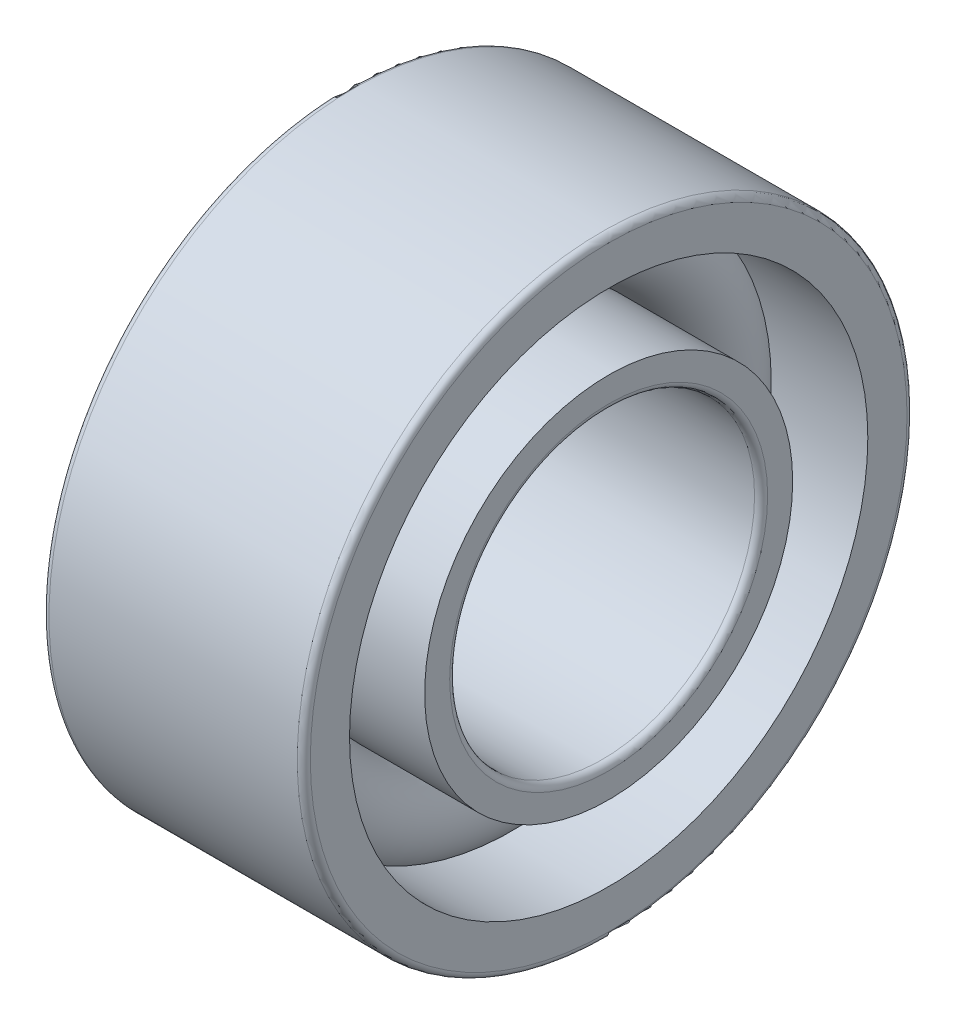
SolidWorks part; units mm, degrees
ref_plane "Plane1" through (0, 0, 0) normal (0, 0, 1) x (1, 0, 0)
ref_plane "Plane2" through (0, 0, 0) normal (0, 1, 0) x (1, 0, 0)
ref_plane "Plane3" through (0, 0, 0) normal (1, 0, 0) x (0, 0, -1)
other "Configuration Table"
sketch "Clipboard" plane through (0, 0, 0) normal (0, 0, 1) x (1, 0, 0)
  line L0 (-10, 0) -> (10, 0) construction
  line L1 (0, 0) -> (22.3471, -0.7804)
  line L2 (0, 0) -> (5.2468, 0.1832)
  line L3 (0, 0) -> (22.3471, -0.7804)
  line L4 (0, 0) -> (-22.3573, -0.3902)
sketch "CagSpiSke" plane through (0, 0, 0) normal (0, 0, 1) x (1, 0, 0)
  line L0 (0.2625, 5.075) -> (0.2625, 5.425)
  line L1 (0.2625, 5.425) -> (-0.2625, 5.425)
  line L2 (-0.2625, 5.425) -> (-0.2625, 5.075)
  line L3 (-0.2625, 5.075) -> (0.2625, 5.075)
  line L4 (-20.6375, 0) -> (20.6375, 0) construction
  line L5 (0, 0) -> (0, 23.7692) construction
revolve "CageSpine" add sketch "CagSpiSke" angle 0.001 about L4
ref_axis "Axis1" through (-50, 0, 0) along (1, 0, 0)
sketch "CagBalSke" plane through (0, 0, 0) normal (0, 0, 1) x (1, 0, 0)
  line L0 (-1.155, 5.25) -> (1.155, 5.25)
  line L1 (-1.905, 5.25) -> (1.905, 5.25) construction
  line L2 (-10, 0) -> (10, 0) construction
  line L3 (0, 0) -> (0, 24) construction
  arc A0 (1.155, 5.25) -> (-1.155, 5.25) centre (0, 5.25) cw
revolve "CageBall" [suppressed] add sketch "CagBalSke" angle 360 about L1 reverse direction yes
pattern_circular "CageBalls" [suppressed] count 2 every 180 about axis through (-50, 0, 0) along (1, 0, 0)
sketch "CagTrmODSke" plane through (0, 0, 0) normal (0, 0, 1) x (1, 0, 0)
  line L0 (1.156, 5.425) -> (1.156, 6.406)
  line L1 (1.156, 6.406) -> (-1.156, 6.406)
  line L2 (-1.156, 6.406) -> (-1.156, 5.425)
  line L3 (-1.156, 5.425) -> (1.156, 5.425)
  line L4 (-20.6375, 0) -> (20.6375, 0) construction
  line L5 (0, 0) -> (0, 25) construction
revolve "CageTrimOD" [suppressed] cut sketch "CagTrmODSke" angle 360 about L4 reverse direction yes
sketch "CagTrmIDSke" plane through (0, 0, 0) normal (0, 0, 1) x (1, 0, 0)
  line L0 (1.156, 4.096) -> (1.156, 5.075)
  line L1 (1.156, 5.075) -> (-1.156, 5.075)
  line L2 (-1.156, 5.075) -> (-1.156, 4.096)
  line L3 (-1.156, 4.096) -> (1.156, 4.096)
  line L4 (-20.6375, 0) -> (20.6375, 0) construction
  line L5 (0, 0) -> (0, 25) construction
revolve "CageTrimID" [suppressed] cut sketch "CagTrmIDSke" angle 360 about L4 reverse direction yes
sketch "BalSimSke" plane through (0, 0, 0) normal (0, 0, 1) x (1, 0, 0)
  line L0 (-10, 0) -> (10, 0) construction
  line L1 (-10, 5.25) -> (10, 5.25) construction
  line L2 (0, 0) -> (0, 23) construction
  circle A0 centre (0, 5.25) radius 1.05
revolve "BallsSimplified" add sketch "BalSimSke" angle 360 about L0
sketch "BalDetSke" plane through (0, 0, 0) normal (0, 0, 1) x (1, 0, 0)
  line L0 (-1.05, 5.25) -> (1.05, 5.25)
  line L1 (-1.905, 5.25) -> (1.905, 5.25) construction
  line L2 (0, 0) -> (0, 25) construction
  arc A0 (1.05, 5.25) -> (-1.05, 5.25) centre (0, 5.25) cw
revolve "BallDetailed" [suppressed] add sketch "BalDetSke" angle 360 about L1 reverse direction yes
sketch "InnRacSke" plane through (0, 0, 0) normal (0, 0, 1) x (1, 0, 0)
  line L0 (-0.7487, 4.55) -> (-3, 4.55)
  line L1 (-3, 4.55) -> (-3, 3.65)
  line L2 (-2.85, 3.5) -> (2.85, 3.5)
  line L3 (3, 3.65) -> (3, 4.225)
  line L4 (0, 4.225) -> (3, 4.225)
  line L5 (-20.6375, 0) -> (20.6375, 0) construction
  line L6 (0, 0) -> (0, 30) construction
  arc A0 (-3, 3.65) -> (-2.85, 3.5) centre (-2.85, 3.65) ccw
  arc A1 (2.85, 3.5) -> (3, 3.65) centre (2.85, 3.65) ccw
  arc A2 (0, 4.225) -> (-0.7487, 4.55) centre (0, 5.25) cw
revolve "InnerRace" add sketch "InnRacSke" angle 360 about L5 reverse direction yes
sketch "OutRacSke" plane through (0, 0, 0) normal (0, 0, 1) x (1, 0, 0)
  line L0 (0, 6.275) -> (-3, 6.275)
  line L1 (-3, 6.275) -> (-3, 6.85)
  line L2 (-2.85, 7) -> (2.85, 7)
  line L3 (3, 6.85) -> (3, 5.95)
  line L4 (3, 5.95) -> (0.7487, 5.95)
  line L5 (-20.6375, 0) -> (20.6375, 0) construction
  line L6 (0, 0) -> (0, 30) construction
  arc A0 (-3, 6.85) -> (-2.85, 7) centre (-2.85, 6.85) cw
  arc A1 (2.85, 7) -> (3, 6.85) centre (2.85, 6.85) cw
  arc A2 (0.7487, 5.95) -> (0, 6.275) centre (0, 5.25) ccw
revolve "OuterRace" add sketch "OutRacSke" angle 360 about L5 reverse direction yes
pattern_circular "BallsDetailed" [suppressed] count 2 every 180 about axis through (-50, 0, 0) along (1, 0, 0)
equation "\"BallCLRad@Clipboard\" = ( \"OD@OutRacSke\" + \"ID@InnRacSke\" ) / 4"
equation "\"BallCLRad@BalSimSke\" = \"BallCLRad@Clipboard\""
equation "\"BallCLRad@BalDetSke\" = \"BallCLRad@Clipboard\""
equation "\"BallCLRad@InnRacSke\" = \"BallCLRad@Clipboard\""
equation "\"BallCLRad@OutRacSke\" = \"BallCLRad@Clipboard\""
equation "\"Ball_diameter@InnRacSke\" = \"Ball_diameter@BalDetSke\" - 0.05"
equation "\"Ball_diameter@OutRacSke\" = \"Ball_diameter@BalDetSke\" - 0.05"
equation "\"Ball_diameter@BalSimSke\" = \"Ball_diameter@BalDetSke\""
equation "\"Width@OutRacSke\" = \"Width@InnRacSke\""
equation "\"Fillet_radius@OutRacSke\" = \"Fillet_radius@InnRacSke\""
equation "\"Max_count@Clipboard\" = int( 3.14159265 / atn(( \"Ball_diameter@BalDetSke\" / 2) / sqr( \"BallCLRad@Clipboard\"  *  \"BallCLRad@Clipboard\" - ( \"Ball_diameter@BalDetSke\" / 2) *  ( \"Ball_diameter@BalDetSke\" / 2))))"
equation "\"Max_count@Clipboard\" = ((sgn( \"Max_count@Clipboard\" - \"Count@Clipboard\" )-1)*( \"Max_count@Clipboard\" - \"Count@Clipboard\" ))/-2+ \"Count@Clipboard\""
equation "\"Count@BallsDetailed\" = int( \"Show_count@Clipboard\" ) "
equation "\"Count@BallsDetailed\" = ((sgn( \"Count@BallsDetailed\" - \"Max_count@Clipboard\" )-1)*( \"Count@BallsDetailed\" - \"Max_count@Clipboard\" ))/-2+ \"Max_count@Clipboard\""
equation "\"Count@BallsDetailed\" = ((sgn( \"Count@BallsDetailed\" - \"Min_count@Clipboard\" )+1)*( \"Count@BallsDetailed\" - \"Min_count@Clipboard\"))/2 +\"Min_count@Clipboard\""
equation "\"Angle@BallsDetailed\" = 360.0 / \"Max_count@Clipboard\""
equation "\"BallCLRad@CagBalSke\" = \"BallCLRad@Clipboard\""
equation "\"Count@CageBalls\" = \"Count@BallsDetailed\""
equation "\"Angle@CageBalls\" = \"Angle@BallsDetailed\""
equation "\"Angle@CageSpine\" =  \"Angle@CageBalls\" * ( \"Count@CageBalls\" -1 + int( \"Count@CageBalls\" / \"Max_count@Clipboard\" ) )  + 0.001 -  int( \"Count@CageBalls\" / \"Max_count@Clipboard\" ) * 0.001"
equation "\"Angle@CageSpine\" =  \"Angle@CageSpine\" * int( \"Min_count@Clipboard\" / 2) + int(1 / \"Min_count@Clipboard\")  * 0.001"
equation "\"CageWallOD@CagBalSke\" =  \"Ball_diameter@BalDetSke\" * 1.1"
equation "\"Thickness@CagSpiSke\" =  \"Ball_diameter@BalDetSke\" * 0.25"
equation "\"OD@CagTrmODSke\" = \"BallCLRad@Clipboard\" * 2 + \"CageWallOD@CagBalSke\" + 0.002"
equation "\"ID@CagTrmODSke\" = \"BallCLRad@Clipboard\" * 2 + \"Ball_diameter@BalDetSke\" / 6"
equation "\"OD@CagTrmIDSke\" = \"BallCLRad@Clipboard\" * 2 - \"Ball_diameter@BalDetSke\" / 6"
equation "\"ID@CagTrmIDSke\" = \"BallCLRad@Clipboard\" * 2 - \"CageWallOD@CagBalSke\" + 0.002"
equation "\"OD@CagSpiSke\" = \"ID@CagTrmODSke\""
equation "\"ID@CagSpiSke\" = \"OD@CagTrmIDSke\""
equation "\"Width@CagTrmODSke\" = \"CageWallOD@CagBalSke\" + 0.002"
equation "\"Width@CagTrmIDSke\" = \"CageWallOD@CagBalSke\" + 0.002"
